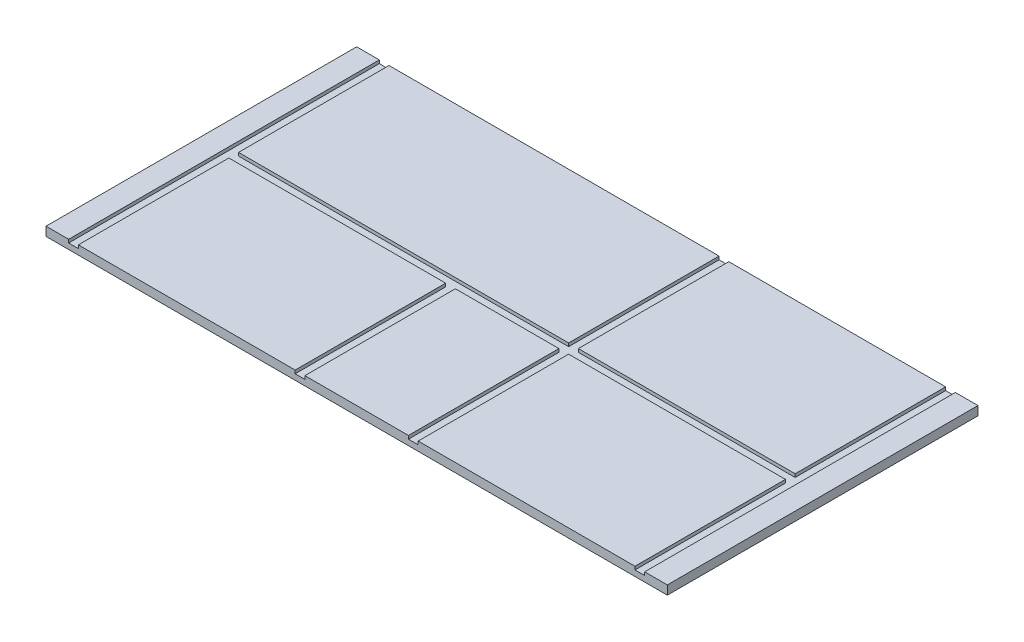
SolidWorks part; units mm, degrees
material "Cedar"
ref_plane "Front Plane" through (0, 0, 0) normal (0, 0, 1) x (1, 0, 0)
ref_plane "Top Plane" through (0, 0, 0) normal (0, 1, 0) x (1, 0, 0)
ref_plane "Right Plane" through (0, 0, 0) normal (1, 0, 0) x (0, 0, -1)
sketch "Sketch1" plane through (0, 0, 0) normal (0, 1, 0) x (1, 0, 0)
  line L1 (-609.6, -304.8) -> (609.6, -304.8)
  line L2 (-609.6, -304.8) -> (-609.6, 304.8)
  line L3 (-609.6, 304.8) -> (609.6, 304.8)
  line L4 (609.6, -304.8) -> (609.6, 304.8)
  line L5 (-609.6, -304.8) -> (609.6, 304.8) construction
  line L6 (-609.6, 304.8) -> (609.6, -304.8) construction
  point P0 (0, 0)
  dimension "D1" = 1219.2
  dimension "D2" = 609.6
extrude "Boss-Extrude1" add sketch "Sketch1" along normal blind 17.4752
sketch "Sketch2" plane through (0, 17.4752, 0) normal (0, 1, 0) x (1, 0, 0)
  line L0 (609.6, 304.8) -> (-609.6, 304.8) construction
  line L1 (-565.15, 304.8) -> (-546.1, 304.8)
  line L2 (-565.15, 304.8) -> (-565.15, -304.8)
  line L3 (-565.15, -304.8) -> (-546.1, -304.8)
  line L4 (-546.1, 304.8) -> (-546.1, 9.525)
  line L5 (-609.6, -304.8) -> (609.6, -304.8) construction
  line L7 (-546.1, 9.525) -> (101.6, 9.525)
  line L8 (-546.1, 9.525) -> (-546.1, -9.525) construction
  line L9 (-546.1, -9.525) -> (-120.65, -9.525)
  line L12 (565.15, 304.8) -> (546.1, 304.8)
  line L13 (565.15, 304.8) -> (565.15, -304.8)
  line L14 (565.15, -304.8) -> (546.1, -304.8)
  line L15 (546.1, 304.8) -> (546.1, 9.525)
  line L17 (-120.65, -9.525) -> (-101.6, -9.525) construction
  line L18 (-120.65, -9.525) -> (-120.65, -304.8)
  line L19 (-120.65, -304.8) -> (-101.6, -304.8)
  line L20 (-101.6, -9.525) -> (-101.6, -304.8)
  line L21 (-546.1, -9.525) -> (-546.1, -304.8)
  line L23 (101.6, -9.525) -> (101.6, -304.8)
  line L24 (101.6, -304.8) -> (120.65, -304.8)
  line L25 (120.65, -9.525) -> (120.65, -304.8)
  line L26 (-101.6, -9.525) -> (101.6, -9.525)
  line L27 (0, 0) -> (0, -9.525) construction
  line L28 (546.1, -9.525) -> (546.1, -304.8)
  line L29 (120.65, -9.525) -> (546.1, -9.525)
  line L30 (-565.15, 304.8) -> (-609.6, 304.8) construction
  line L31 (565.15, 304.8) -> (609.6, 304.8) construction
  line L32 (-609.6, 304.8) -> (-609.6, -304.8) construction
  line L33 (120.65, 9.525) -> (546.1, 9.525)
  line L35 (101.6, 9.525) -> (101.6, 304.8)
  line L36 (101.6, 304.8) -> (120.65, 304.8)
  line L37 (120.65, 9.525) -> (120.65, 304.8)
  line L38 (-546.1, 0) -> (-609.6, 0) construction
  dimension "D1" = 19.05
  dimension "D3" = 425.45
  dimension "D4" = 203.2
  dimension "D5" = 44.45
extrude "Cut-Extrude1" cut sketch "Sketch2" against normal blind 6.35
